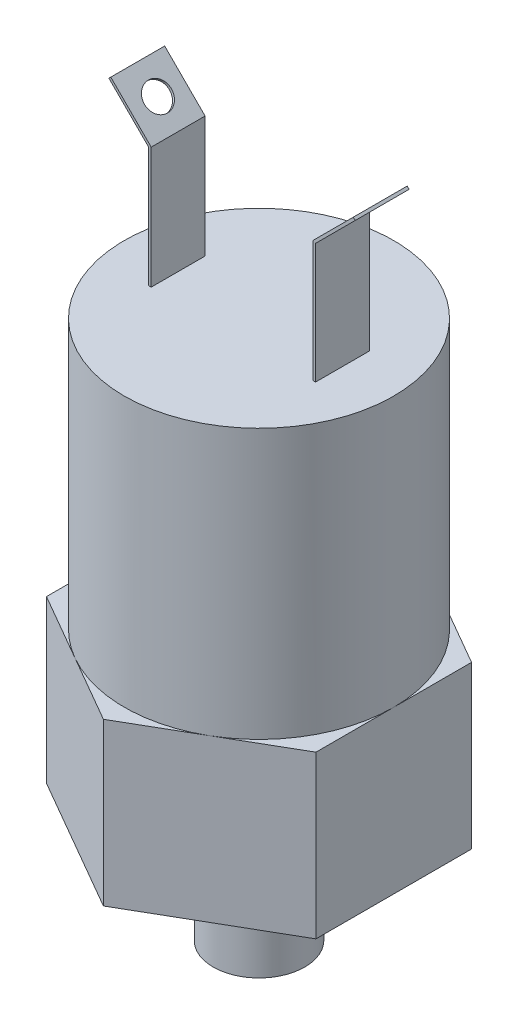
SolidWorks part; units mm, degrees
ref_plane "Front Plane" through (0, 0, 0) normal (0, 0, 1) x (1, 0, 0)
ref_plane "Top Plane" through (0, 0, 0) normal (0, 1, 0) x (1, 0, 0)
ref_plane "Right Plane" through (0, 0, 0) normal (1, 0, 0) x (0, 0, -1)
sketch "Sketch1" plane through (0, 0, 0) normal (0, 1, 0) x (1, 0, 0)
  circle A0 centre (0, 0) radius 4.318
  dimension "D1" = 8.636
extrude "Boss-Extrude1" add sketch "Sketch1" along normal blind 10.16
cosmetic thread "Cosmetic Thread1" parameters "D2"=7.636
sketch "Sketch2" plane through (0, 10.16, 0) normal (0, 1, 0) x (1, 0, 0)
  line L1 (0, 14.6647) -> (-12.7, 7.3323)
  line L2 (-12.7, 7.3323) -> (-12.7, -7.3323)
  line L3 (-12.7, -7.3323) -> (0, -14.6647)
  line L4 (0, -14.6647) -> (12.7, -7.3323)
  line L5 (12.7, -7.3323) -> (12.7, 7.3323)
  line L6 (12.7, 7.3323) -> (0, 14.6647)
  circle A0 centre (0, 0) radius 12.7 construction
  dimension "D1" = 25.4
extrude "Boss-Extrude2" add sketch "Sketch2" along normal blind 15.24
sketch "Sketch3" plane through (0, 25.4, 0) normal (0, 1, 0) x (1, 0, 0)
  circle A0 centre (0, 0) radius 12.7
  dimension "D1" = 25.4
extrude "Boss-Extrude3" add sketch "Sketch3" along normal blind 25.4
sketch "Sketch4" plane through (0, 0, 0) normal (0, 0, 1) x (1, 0, 0)
  line L0 (7.62, 50.8) -> (7.62, 62.23)
  line L1 (12.7, 50.8) -> (-12.7, 50.8) construction
  line L2 (7.62, 62.23) -> (11.43, 66.04)
  line L3 (12.7, 25.4) -> (12.7, 50.8) construction
  dimension "D1" = 15.24
  dimension "D2" = 45
  dimension "D3" = 11.43
  dimension "D4" = 5.08
extrude "Extrude-Thin1" add sketch "Sketch4" along normal mid plane 5.08 thin thin type one direction wall 0.254
sketch "Sketch5" plane through (-27.305, 27.305, 0) normal (-0.7071, 0.7071, 0) x (0, 0, 1)
  line L0 (-2.54, 54.7796) -> (2.54, 49.3914) construction
  line L1 (2.54, 54.7796) -> (-2.54, 49.3914) construction
  circle A0 centre (0, 52.0855) radius 1.27
  dimension "D1" = 2.54
extrude "Cut-Extrude1" cut sketch "Sketch5" against normal up to next
mirror "Mirror1" about plane through (0, 0, 0) normal (1, 0, 0) of "Cut-Extrude1", "Extrude-Thin1"
